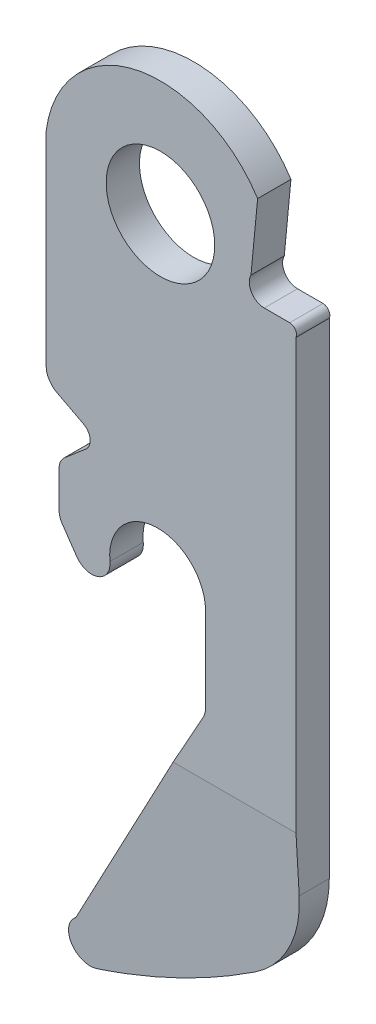
SolidWorks part; units mm, degrees
ref_plane "Front Plane" through (0, 0, 0) normal (0, 0, 1) x (1, 0, 0)
ref_plane "Top Plane" through (0, 0, 0) normal (0, 1, 0) x (1, 0, 0)
ref_plane "Right Plane" through (0, 0, 0) normal (1, 0, 0) x (0, 0, -1)
sketch "Sketch1" plane through (0, 0, 0) normal (0, 0, 1) x (1, 0, 0)
  line L0 (20.2608, 45.5867) -> (101.3038, 45.5867) construction
  line L1 (70.4187, 59.1709) -> (70.4187, 40.6671)
  line L2 (60.8937, 61.2292) -> (60.8937, 53.0041)
  line L3 (68.9562, 63.0241) -> (68.7028, 60.37)
  line L4 (69.2084, 59.5371) -> (70.1802, 59.5371)
  line L5 (60.8937, 53.0041) -> (62.3151, 52.2635)
  line L6 (62.4036, 51.4747) -> (61.6034, 50.7956)
  line L7 (61.3842, 50.3219) -> (61.3842, 48.9587)
  line L8 (61.5085, 48.5573) -> (62.0567, 47.7578)
  line L9 (66.9713, 48.4115) -> (66.9713, 45.0819)
  line L10 (66.9713, 45.0207) -> (61.5971, 35.3899)
  line L12 (66.9713, 45.0819) -> (66.9713, 45.0207)
  arc A1 (68.7028, 60.37) -> (69.2084, 59.5371) centre (69.2084, 60.107) ccw
  arc A2 (70.4187, 59.1709) -> (70.1802, 59.5371) centre (70.1759, 59.2736) ccw
  arc A4 (62.4036, 51.4747) -> (62.3151, 52.2635) centre (62.0941, 51.8393) ccw
  arc A5 (61.6034, 50.7956) -> (61.3842, 50.3219) centre (62.0055, 50.3219) ccw
  arc A6 (61.3842, 48.9587) -> (61.5085, 48.5573) centre (62.0941, 48.9587) ccw
  arc A7 (62.0567, 47.7578) -> (63.325, 48.2236) centre (62.6316, 48.152) ccw
  arc A8 (66.9713, 48.4115) -> (63.325, 48.2236) centre (65.1433, 48.4115) ccw
  arc A10 (61.5971, 35.3899) -> (62.318, 34.0236) centre (62.0661, 34.764) ccw
  arc A11 (68.5259, 37.1058) -> (70.4187, 40.6671) centre (66.1221, 40.6671) ccw
  arc A12 (62.318, 34.0236) -> (68.5259, 37.1058) centre (53.8941, 58.7826) ccw
  arc A13 (68.9562, 63.0241) -> (60.8937, 61.2292) centre (65.2507, 60.6631) ccw
  point P3 (0, 0)
  point P17 (0, 0)
  point P18 (66.9843, 45.1627)
  point P22 (0, 0)
  point P25 (0, 0)
  point P28 (66.9847, 44.4844)
  point P32 (60.8937, 52.7946)
  point P35 (66.9713, 45.0164)
  point P38 (60.8937, 53.0041)
  dimension "D1" = 9.525
  dimension "D2" = 4.3937
  dimension "D4" = 0.5699
  dimension "D6" = 4.2966
  dimension "D7" = 0.7821
  dimension "D8" = 1.828
  dimension "D9" = 3.3296
  dimension "D10" = 0.6971
  dimension "D11" = 0.4783
  dimension "D12" = 8.2251
  dimension "D3" = 3.487
  dimension "D5" = 24.7731
  dimension "D13" = 1.3631
extrude "Boss-Extrude1" add sketch "Sketch1" along normal blind 1.27
sketch "Sketch2" plane through (0, 0, 1.27) normal (0, 0, 1) x (1, 0, 0)
  circle A0 centre (65.2507, 60.6631) radius 2.0701
  dimension "D1" = 4.1402
extrude "Cut-Extrude1" cut sketch "Sketch2" against normal through all
fillet "Fillet1" radius 0.762 2 edges at (60.8937, 53.0041, 0.635) (66.9713, 45.0207, 0.635)
sketch "Sketch3" plane through (70.4187, 0, 0) normal (1, 0, 0) x (0, 0, -1)
  line L8 (-1.27, 33.9819) -> (-0.762, 33.9819)
  line L9 (-1.27, 33.9819) -> (0, 33.9819) construction
  line L10 (-0.762, 33.9819) -> (-1.27, 42.8067)
  line L11 (-1.27, 40.6671) -> (-1.27, 59.1709) construction
  line L12 (-1.27, 42.8067) -> (-1.27, 33.9819)
  line L13 (0, 34.0236) -> (0, 37.1058) construction
  dimension "D1" = 0.762
  dimension "D2" = 3.295
extrude "Cut-Extrude2" cut sketch "Sketch3" against normal through all
